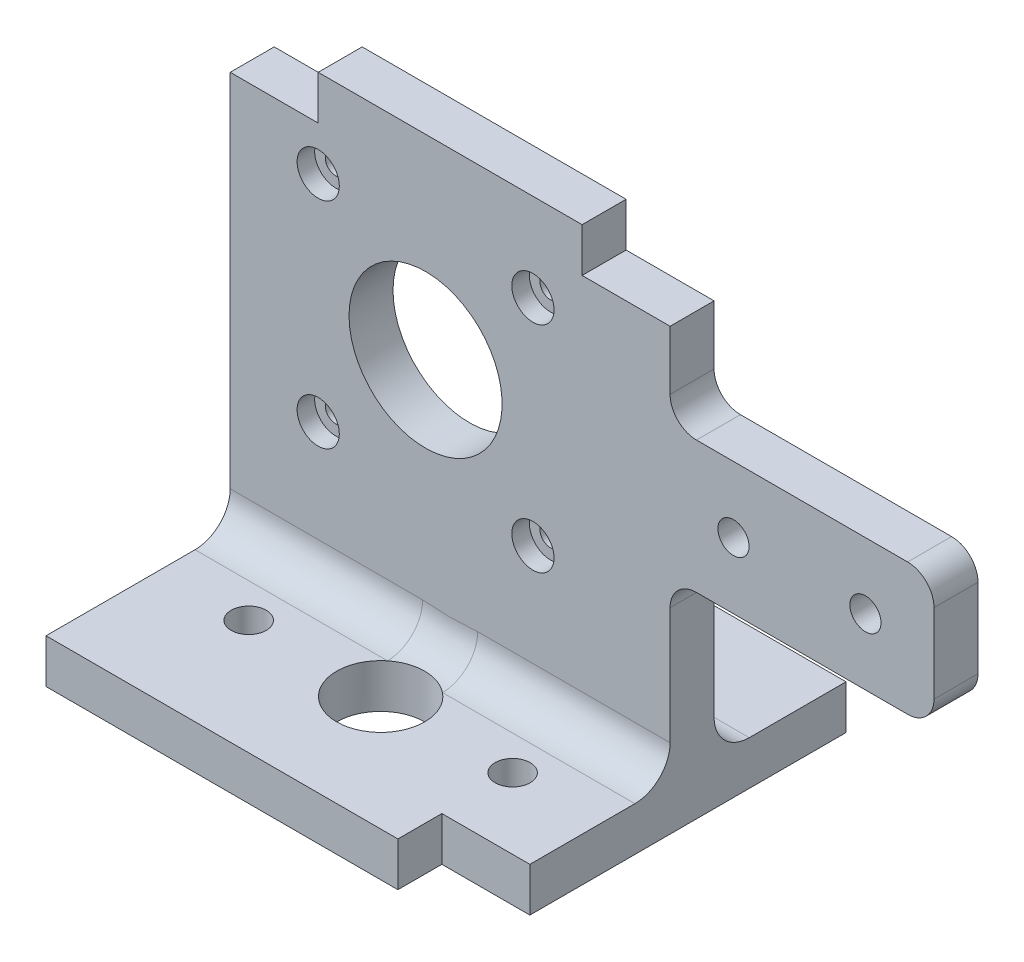
SolidWorks part; units mm, degrees
other "Markup1"
sketch "Sketch24" plane through (-71.7031, 34.925, 32.9438) normal (-0.7733, 0.3379, 0.5366) x (0.6154, 0.1961, 0.7634)
ref_plane "Front Plane" through (0, 0, 0) normal (0, 0, 1) x (1, 0, 0)
ref_plane "Top Plane" through (0, 0, 0) normal (0, 1, 0) x (1, 0, 0)
ref_plane "Right Plane" through (0, 0, 0) normal (1, 0, 0) x (0, 0, -1)
sketch "Sketch1" plane through (0, 0, 0) normal (0, 0, 1) x (1, 0, 0)
  line L1 (-50.8, 34.925) -> (50.8, 34.925)
  line L2 (-50.8, 34.925) -> (-50.8, -34.925)
  line L3 (-50.8, -34.925) -> (50.8, -34.925)
  line L4 (50.8, 34.925) -> (50.8, -34.925)
  point P4 (-50.8, 0)
  point P5 (0, 34.925)
  dimension "D1" = 101.6
  dimension "D2" = 69.85
extrude "Boss-Extrude1" add sketch "Sketch1" along normal blind 6.35
sketch "Sketch2" plane through (0, 0, 6.35) normal (0, 0, 1) x (1, 0, 0)
  line L0 (-50.8, 34.925) -> (-50.8, -34.925) construction
  line L1 (-50.8, -28.575) -> (12.7, -28.575)
  line L2 (-50.8, -28.575) -> (-50.8, -34.925)
  line L3 (-50.8, -34.925) -> (12.7, -34.925)
  line L4 (12.7, -28.575) -> (12.7, -34.925)
  line L5 (-50.8, -34.925) -> (50.8, -34.925) construction
  dimension "D1" = 63.5
  dimension "D2" = 6.35
extrude "Boss-Extrude2" add sketch "Sketch2" along normal blind 26.5938 and the other way blind 25.4
hole_wizard "Hole2" positions "Sketch5" profile "Sketch6" legacy
sketch "Sketch5" plane through (0, 0, 6.35) normal (0, 0, 1) x (1, 0, 0)
  line L1 (-50.8, 34.925) -> (-50.8, -28.575) construction
  line L3 (50.8, 34.925) -> (-50.8, 34.925) construction
  point P0 (-38.1, 22.225)
  point P2 (-7.1018, 22.225)
  point P4 (-7.1018, -8.7732)
  point P6 (-38.1, -8.7732)
  dimension "D1" = 30.9982
  dimension "D2" = 30.9982
  dimension "D3" = 12.7
  dimension "D4" = 12.7
sketch "Sketch6" plane through (-38.1, 22.225, 6.35) normal (1, 0, 0) x (0, -1, 0)
  line L0 (0, 0) -> (0, 6.35)
  line L1 (0, 6.35) -> (1.524, 6.35)
  line L2 (1.524, 6.35) -> (1.524, 2.54)
  line L3 (1.524, 2.54) -> (3.048, 2.54)
  line L4 (3.048, 2.54) -> (3.048, 0)
  line L5 (3.048, 0) -> (0, 0)
  line L6 (0, 110) -> (0, -10) construction
  dimension "Diameter" = 3.048
  dimension "Depth" = 6.35
  dimension "C-Bore Diameter" = 6.096
  dimension "C-Bore Depth" = 2.54
sketch "Sketch7" plane through (0, 0, 0) normal (0, 0, -1) x (-1, 0, 0)
  line L0 (7.1018, 22.225) -> (38.1, 22.225) construction
  line L1 (38.1, 22.225) -> (38.1, -8.7732) construction
  circle A0 centre (22.6009, 6.7259) radius 11.049
  point P9 (22.6009, 22.225)
  point P10 (38.1, 6.7259)
  point P11 (22.6009, 6.7259)
  dimension "D1" = 22.098
extrude "Cut-Extrude1" cut sketch "Sketch7" against normal up to surface (6.35 mm away) up to face at (-35.052, 22.225, 6.35)
hole_wizard "M4 Clearance Hole2" positions "Sketch8" profile "Sketch10" hole size "M4" standard "ANSI Metric"
sketch "Sketch8" plane through (0, 0, 0) normal (0, 0, -1) x (-1, 0, 0)
  line L0 (38.1, 22.225) -> (7.1018, -8.7732) construction
  line L2 (7.1018, 22.225) -> (38.1, -8.7732) construction
  point P0 (-21.8491, 6.7259)
  point P2 (-40.8991, 6.7259)
  point P17 (22.6009, 6.7259)
  dimension "D1" = 19.05
  dimension "D2" = 44.45
sketch "Sketch10" plane through (21.8491, 6.7259, 0) normal (1, 0, 0) x (0, 1, 0)
  line L0 (0, 0) -> (0, 7.7019)
  line L1 (0, 7.7019) -> (2.25, 6.35)
  line L2 (2.25, 6.35) -> (2.25, 0)
  line L5 (2.25, 0) -> (0, 0)
  line L10 (0, 7.7019) -> (-2.25, 6.35) construction
  line L11 (0, -6.35) -> (0, 107.95) construction
  dimension "Hole Dia." = 4.5
  dimension "Hole Depth" = 6.35
  dimension "Drill Angle" = 118
sketch "Sketch15" plane through (0, 0, 0) normal (0, 0, -1) x (-1, 0, 0)
  line L0 (22.6009, 6.7259) -> (22.6009, -49.0147) construction
sketch "Sketch16" plane through (0, -34.925, 0) normal (0, -1, 0) x (1, 0, 0)
  line L0 (12.7, 6.35) -> (-50.8, 6.35) construction
  line L1 (-50.8, 32.9438) -> (-50.8, -19.05) construction
  circle A0 centre (-19.05, 16.383) radius 6.35
  dimension "D1" = 12.7
  dimension "D2" = 10.033
  dimension "D3" = 31.75
extrude "Cut-Extrude3" cut sketch "Sketch16" against normal up to surface (6.35 mm away) up to face at (-19.05, -28.575, 19.6469)
sketch "Sketch21" plane through (0, -28.575, 0) normal (0, 1, 0) x (1, 0, 0)
  line L0 (6.3573, -16.383) -> (-71.7031, -16.383) construction
hole_wizard "#8 (0.199) Diameter Hole1" positions "Sketch22" profile "Sketch23" hole size "#8" standard "ANSI Inch" end condition through all
sketch "Sketch22" plane through (0, -28.575, 0) normal (0, 1, 0) x (1, 0, 0)
  line L0 (6.3573, -16.383) -> (-71.7031, -16.383) construction
  circle A0 centre (-19.05, -16.383) radius 6.35 construction
  point P0 (-38.1, -16.383)
  point P2 (0, -16.383)
  dimension "D1" = 19.05
  dimension "D2" = 19.05
sketch "Sketch23" plane through (-38.1, -28.575, 16.383) normal (1, 0, 0) x (0, 0, 1)
  line L0 (0, 0) -> (0, 6.35)
  line L1 (0, 6.35) -> (2.5273, 6.35)
  line L2 (2.5273, 6.35) -> (2.5273, 0)
  line L5 (2.5273, 0) -> (0, 0)
  line L11 (0, -6.35) -> (0, 107.95) construction
  dimension "Thru Hole Dia." = 5.0546
  dimension "Thru Hole Depth" = 6.35
sketch "Sketch25" plane through (0, 0, 6.35) normal (0, 0, 1) x (1, 0, 0)
  line L0 (12.7, -34.925) -> (12.7, -2.7991)
  line L1 (12.7, -2.7991) -> (50.8, -2.7991)
  line L2 (50.8, -34.925) -> (50.8, 34.925) construction
  line L4 (50.8, 16.2509) -> (12.7, 16.2509)
  line L5 (12.7, 16.2509) -> (12.7, 34.925)
  line L6 (50.8, 34.925) -> (-50.8, 34.925) construction
  line L7 (21.8491, 6.7259) -> (68.6745, 6.7259) construction
  line L8 (12.7, -34.925) -> (50.8, -34.925) construction
  line L9 (12.7, -34.925) -> (50.8, -34.925)
  line L10 (50.8, -34.925) -> (50.8, -2.7991)
  line L11 (50.8, 34.925) -> (12.7, 34.925)
  line L12 (50.8, 16.2509) -> (50.8, 34.925)
  line L13 (50.8, 16.2509) -> (50.8, -2.7991) construction
  point P2 (50.8, 6.7259)
  dimension "D1" = 19.05
extrude "Cut-Extrude4" cut sketch "Sketch25" against normal up to surface (6.35 mm away) up to face at (19.5991, 6.7259, 0)
fillet "Fillet1" radius 3.81 4 edges at (50.8, 16.2509, 3.175) (12.7, 16.2509, 3.175) (12.7, -2.7991, 3.175) (50.8, -2.7991, 3.175)
sketch "Sketch26" plane through (0, 0, 6.35) normal (0, 0, 1) x (1, 0, 0)
  line L1 (12.7, 34.925) -> (0, 34.925)
  line L2 (12.7, 34.925) -> (12.7, 28.575)
  line L3 (12.7, 28.575) -> (0, 28.575)
  line L4 (0, 34.925) -> (0, 28.575)
  line L5 (-50.8, 34.925) -> (-38.1, 34.925)
  line L6 (-50.8, 34.925) -> (-50.8, 28.575)
  line L7 (-50.8, 28.575) -> (-38.1, 28.575)
  line L8 (-38.1, 34.925) -> (-38.1, 28.575)
  dimension "D1" = 6.35
  dimension "D2" = 12.7
  dimension "D3" = 12.7
extrude "Cut-Extrude5" cut sketch "Sketch26" against normal up to surface (6.35 mm away) up to face at (19.5991, 6.7259, 0)
sketch "Sketch27" plane through (0, -28.575, 0) normal (0, 1, 0) x (1, 0, 0)
  line L1 (12.7, -32.9438) -> (0, -32.9438)
  line L2 (12.7, -32.9438) -> (12.7, -26.5938)
  line L3 (12.7, -26.5938) -> (0, -26.5938)
  line L4 (0, -32.9438) -> (0, -26.5938)
  dimension "D1" = 6.35
  dimension "D2" = 12.7
extrude "Cut-Extrude6" cut sketch "Sketch27" against normal up to surface (6.35 mm away) up to face at (-38.1, -34.925, 18.9103)
fillet "Fillet2" radius 5.08 2 edges at (-19.05, -28.575, 6.35) (-19.05, -28.575, 0)
